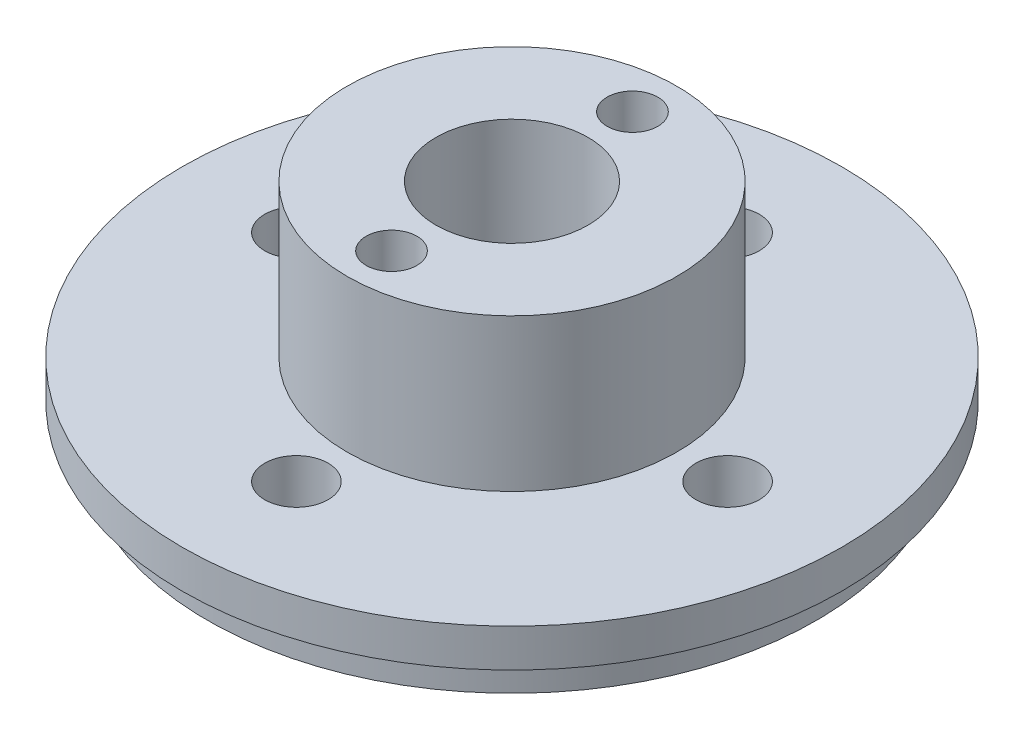
SolidWorks part; units mm, degrees
ref_plane "Front Plane" through (0, 0, 0) normal (0, 0, 1) x (1, 0, 0)
ref_plane "Top Plane" through (0, 0, 0) normal (0, 1, 0) x (1, 0, 0)
ref_plane "Right Plane" through (0, 0, 0) normal (1, 0, 0) x (0, 0, -1)
sketch "Sketch1" plane through (0, 0, 0) normal (0, 1, 0) x (1, 0, 0)
  circle A0 centre (0, 0) radius 13
extrude "Boss-Extrude1" add sketch "Sketch1" along normal blind 1.5
sketch "Sketch2" plane through (0, 1.5, 0) normal (0, 1, 0) x (1, 0, 0)
  circle A0 centre (0, 0) radius 6.5
extrude "Boss-Extrude2" add sketch "Sketch2" along normal blind 6
sketch "Sketch3" plane through (0, 7.5, 0) normal (0, 1, 0) x (1, 0, 0)
  circle A0 centre (0, 0) radius 3
extrude "Cut-Extrude1" cut sketch "Sketch3" against normal blind 6
sketch "Sketch4" plane through (0, 0, 0) normal (0, -1, 0) x (1, 0, 0)
  circle A1 centre (0, 0) radius 8.5 construction
  circle A2 centre (-8.5, 0) radius 1.25
  circle A3 centre (0, 8.5) radius 1.25
  circle A4 centre (8.5, 0) radius 1.25
  circle A5 centre (0, -8.5) radius 1.25
  point P15 (0, 0)
  dimension "D1" = 4
extrude "Cut-Extrude5" cut sketch "Sketch4" against normal mid plane 16
sketch "Sketch6" plane through (0, 7.5, 0) normal (0, 1, 0) x (1, 0, 0)
  circle A1 centre (0, 4.75) radius 1
  circle A2 centre (0, -4.75) radius 1
  point P6 (-7.25, 0)
extrude "Cut-Extrude6" cut sketch "Sketch6" against normal blind 6
sketch "Sketch7" plane through (0, 0, 0) normal (0, -1, 0) x (1, 0, 0)
  circle A0 centre (0, 0) radius 12
  circle A1 centre (0, 0) radius 2
extrude "Boss-Extrude3" add sketch "Sketch7" along normal blind 1.5
sketch "Sketch8" plane through (0, -1.5, 0) normal (0, -1, 0) x (1, 0, 0)
  circle A0 centre (0, 0) radius 6.5
  circle A1 centre (0, 0) radius 2
extrude "Boss-Extrude4" add sketch "Sketch8" along normal blind 0.8
sketch "Sketch9" plane through (0, 0, 0) normal (0, 1, 0) x (1, 0, 0)
  circle A0 centre (8.5, 0) radius 1.25
  circle A1 centre (0, -8.5) radius 1.25
  circle A2 centre (-8.5, 0) radius 1.25
  circle A3 centre (0, 8.5) radius 1.25
  point P12 (0, 0)
  dimension "D1" = 4
extrude "Cut-Extrude8" cut sketch "Sketch9" against normal blind 10.8
sketch "Sketch10" plane through (0, 0, 0) normal (0, -1, 0) x (1, 0, 0)
  circle A0 centre (0, 0) radius 2
extrude "Cut-Extrude9" cut sketch "Sketch10" against normal blind 10.8
sketch "Sketch11" plane through (0, -2.3, 0) normal (0, -1, 0) x (1, 0, 0)
  line L1 (0, 0) -> (-16.0044, 0)
  line L2 (1.9445, 1.9445) -> (-8.3202, 12.2093)
  line L3 (-1.9445, -1.9445) -> (-12.2093, 8.3202)
  line L4 (0, 3.8891) -> (-3.8891, 0)
  line L5 (-3.8891, 0) -> (-8.3202, 4.4312)
  line L6 (-8.3202, 4.4312) -> (-4.4312, 8.3202)
  line L7 (-4.4312, 8.3202) -> (0, 3.8891)
  circle M3 centre (0, 0) radius 6.5
extrude "Cut-Extrude10" cut sketch "Sketch11" against normal blind 0.8 contours L4 L2 L3 M3 region at (-3.2031, -2.3, 3.2031)
chamfer "Chamfer4" distance 1 angle 45 1 edges at (0, 1.5, 2)
